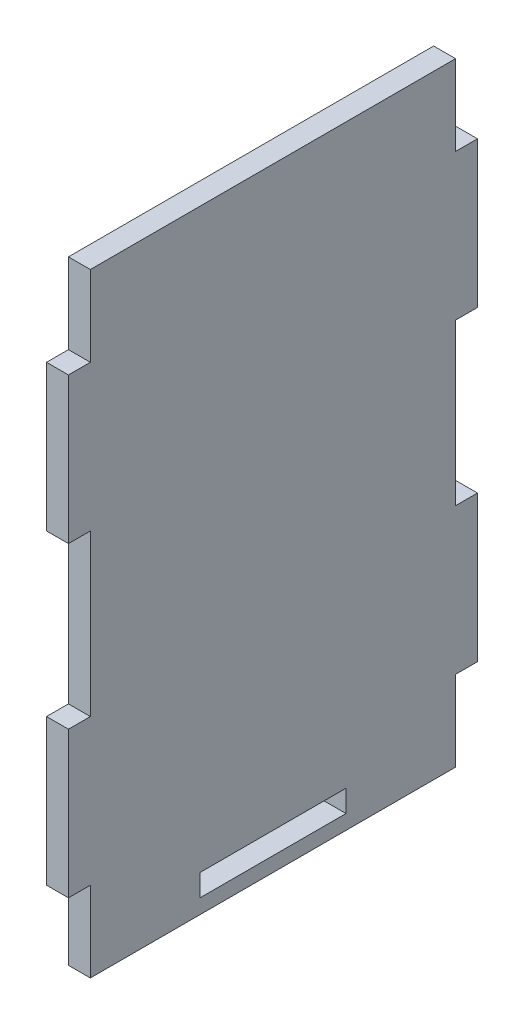
SolidWorks part; units mm, degrees
ref_plane "Front Plane" through (0, 0, 0) normal (0, 0, 1) x (1, 0, 0)
ref_plane "Top Plane" through (0, 0, 0) normal (0, 1, 0) x (1, 0, 0)
ref_plane "Right Plane" through (0, 0, 0) normal (1, 0, 0) x (0, 0, -1)
sketch "Sketch1" plane through (0, 0, 0) normal (1, 0, 0) x (0, 0, -1)
  line L0 (0, 0) -> (0, 3.5) construction
  line L1 (0, 0) -> (50, 0)
  line L2 (0, 0) -> (0, 11)
  line L3 (0, 84) -> (50, 84)
  line L4 (50, 0) -> (50, 11)
  line L5 (0, 3.5) -> (50, 3.5) construction
  line L6 (50, 84) -> (50, 73) construction
  line L7 (15, 2) -> (35, 2)
  line L8 (15, 2) -> (15, 5)
  line L9 (15, 5) -> (35, 5)
  line L10 (35, 2) -> (35, 5)
  line L11 (15, 2) -> (35, 5) construction
  line L12 (15, 5) -> (35, 2) construction
  line L13 (50, 42) -> (50, 53) construction
  line L14 (50, 42) -> (50, 53) construction
  line L15 (50, 42) -> (0, 42) construction
  line L16 (50, 53) -> (53, 53)
  line L18 (50, 73) -> (53, 73)
  line L19 (53, 53) -> (53, 73)
  line L20 (50, 31) -> (50, 53)
  line L21 (50, 11) -> (50, 0) construction
  line L22 (25, 42) -> (25, 84) construction
  line L23 (50, 31) -> (53, 31)
  line L25 (53, 31) -> (53, 11)
  line L26 (50, 11) -> (53, 11)
  line L28 (0, 11) -> (-3, 11)
  line L29 (-3, 31) -> (-3, 11)
  line L30 (0, 31) -> (-3, 31)
  line L31 (0, 73) -> (-3, 73)
  line L32 (-3, 53) -> (-3, 73)
  line L33 (0, 53) -> (-3, 53)
  line L35 (50, 73) -> (50, 84)
  line L36 (50, 53) -> (50, 31) construction
  line L37 (50, 73) -> (50, 84) construction
  line L38 (50, 73) -> (50, 84) construction
  line L39 (0, 31) -> (0, 53)
  line L40 (0, 73) -> (0, 84)
  line L41 (50, 73) -> (53, 53) construction
  line L42 (50, 53) -> (53, 73) construction
  line L43 (39.224, 84) -> (39.224, 0) construction
  line L44 (39.224, 42) -> (39.224, 84) construction
  line L45 (51.5, 63) -> (39.224, 63) construction
  point P5 (25, 3.5)
  dimension "D1" = 84
  dimension "D2" = 50
  dimension "D3" = 20
  dimension "D4" = 3
  dimension "D5" = 2
  dimension "D6" = 20
extrude "Boss-Extrude2" add sketch "Sketch1" along normal blind 3
